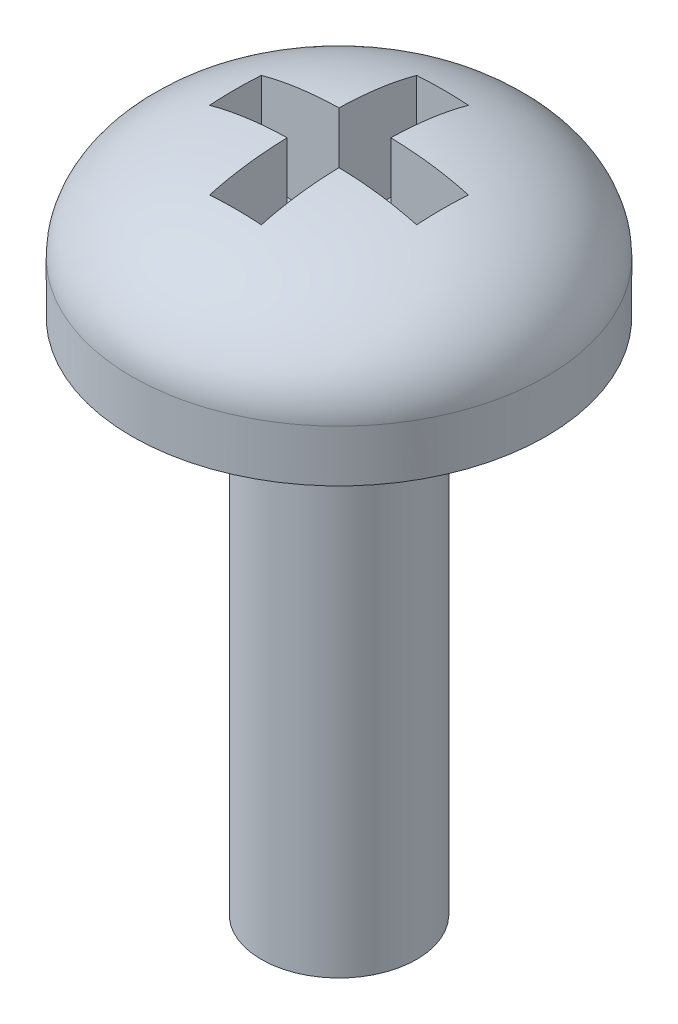
SolidWorks part; units mm, degrees
ref_plane "Front Plane" through (0, 0, 0) normal (0, 0, 1) x (1, 0, 0)
ref_plane "Top Plane" through (0, 0, 0) normal (0, 1, 0) x (1, 0, 0)
ref_plane "Right Plane" through (0, 0, 0) normal (1, 0, 0) x (0, 0, -1)
sketch "Sketch1" plane through (0, 0, 0) normal (0, 1, 0) x (1, 0, 0)
  circle A0 centre (0, 0) radius 1.5
  dimension "D1" = 3
extrude "Boss-Extrude1" add sketch "Sketch1" along normal blind 10
sketch "Sketch2" plane through (0, 10, 0) normal (0, 1, 0) x (1, 0, 0)
  circle A0 centre (0, 0) radius 4
  dimension "D1" = 8
extrude "Boss-Extrude2" add sketch "Sketch2" along normal blind 3
sketch "Sketch3" plane through (0, 13, 0) normal (0, 1, 0) x (1, 0, 0)
  line L1 (-0.5, -2) -> (0.5, -2)
  line L2 (-0.5, -2) -> (-0.5, 2)
  line L3 (-0.5, 2) -> (0.5, 2)
  line L4 (0.5, -2) -> (0.5, 2)
  line L5 (-0.5, -2) -> (0.5, 2) construction
  line L6 (-0.5, 2) -> (0.5, -2) construction
  line L7 (-2, -0.5) -> (2, -0.5)
  line L8 (-2, -0.5) -> (-2, 0.5)
  line L9 (-2, 0.5) -> (2, 0.5)
  line L10 (2, -0.5) -> (2, 0.5)
  line L11 (-2, -0.5) -> (2, 0.5) construction
  line L12 (-2, 0.5) -> (2, -0.5) construction
  point P0 (0, 0)
  point P6 (0, 0)
  dimension "D1" = 1
  dimension "D2" = 4
  dimension "D3" = 4
  dimension "D4" = 1
extrude "Cut-Extrude1" cut sketch "Sketch3" against normal blind 2 contours L9 L8 L7 L2 | L9 L2 L7 L4 | L2 L9 L4 L3 | L7 L10 L9 L4 | L7 L2 L1 L4 region at (0, 13, 1.25) region at (-1.25, 13, 0) region at (0, 13, 0) region at (1.25, 13, 0) region at (0, 13, -1.25)
fillet "Fillet1" radius 2 1 edges at (0, 13, 4) second distance 3.5 first distance on face at (0, 13, 4)
